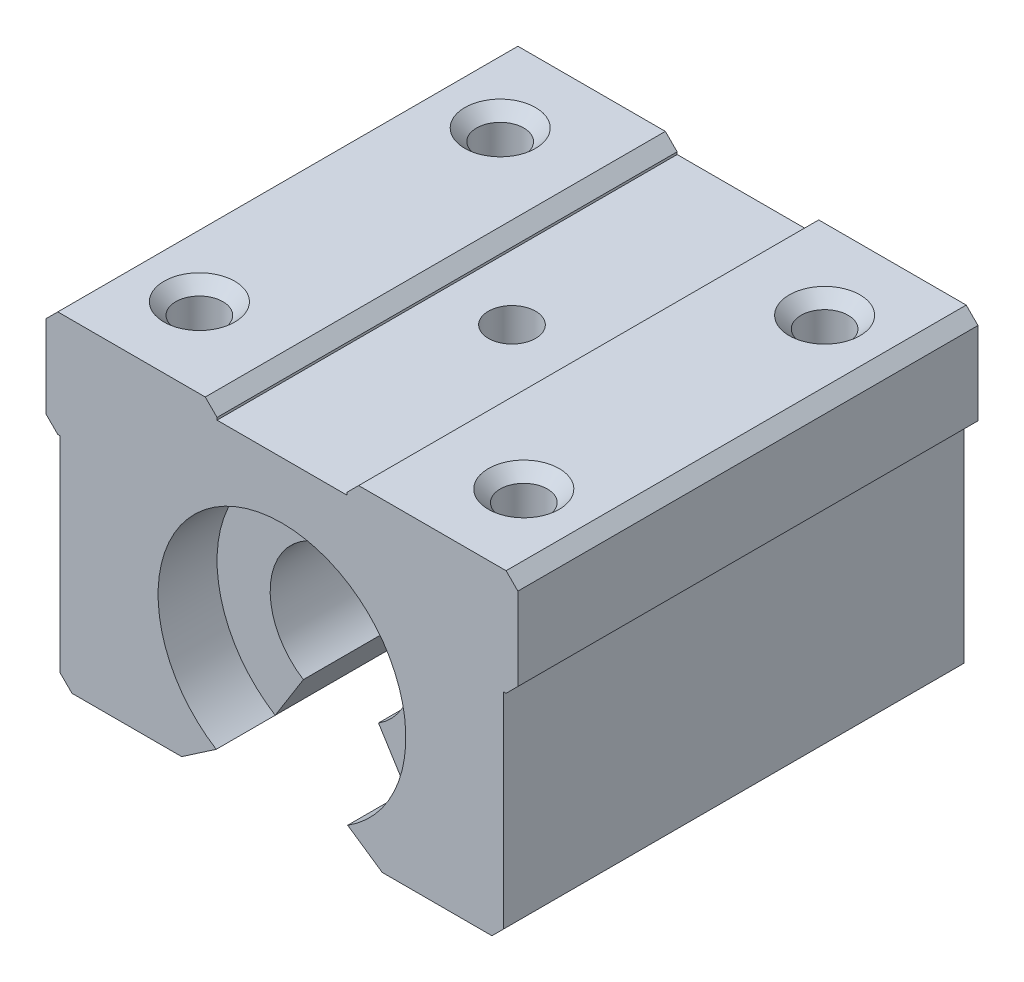
SolidWorks part; units mm, degrees
material "Aleación 1060"
ref_plane "Alzado" through (0, 0, 0) normal (0, 0, 1) x (1, 0, 0)
ref_plane "Planta" through (0, 0, 0) normal (0, 1, 0) x (1, 0, 0)
ref_plane "Vista lateral" through (0, 0, 0) normal (1, 0, 0) x (0, 0, -1)
sketch "Croquis1" plane through (0, 0, 0) normal (0, 0, 1) x (1, 0, 0)
  line L0 (-18.8, -12.5) -> (-18.8, 12.5) construction
  line L1 (-20, -13.7) -> (20, -13.7) construction
  line L2 (-20, -13.7) -> (-20, 13.7) construction
  line L3 (-20, 13.7) -> (20, 13.7) construction
  line L4 (20, -13.7) -> (20, 13.7) construction
  line L5 (-20, -13.7) -> (20, 13.7) construction
  line L6 (-20, 13.7) -> (20, -13.7) construction
  line L7 (-18.8, 12.5) -> (18.8, 12.5) construction
  line L8 (18.8, -12.5) -> (18.8, 12.5) construction
  line L9 (-18.8, -12.5) -> (18.8, -12.5) construction
  line L10 (-5.5, 13.7) -> (-5.5, -13.7) construction
  line L11 (5.5, 13.7) -> (5.5, -13.7) construction
  line L12 (-20, 4.7) -> (20, 4.7) construction
  line L13 (-5.5, 13.7) -> (-5.5, 12.5)
  line L14 (-5.5, 12.5) -> (5.5, 12.5)
  line L15 (5.5, 12.5) -> (5.5, 13.7)
  line L16 (5.5, 13.7) -> (20, 13.7)
  line L17 (20, 13.7) -> (20, 4.7)
  line L18 (20, 4.7) -> (18.8, 4.7)
  line L19 (18.8, 4.7) -> (18.8, -13.7)
  line L20 (18.8, -13.7) -> (-18.8, -13.7)
  line L21 (-18.8, -13.7) -> (-18.8, 4.7)
  line L22 (-18.8, 4.7) -> (-20, 4.7)
  line L23 (-20, 4.7) -> (-20, 13.7)
  line L24 (-20, 13.7) -> (-5.5, 13.7)
  point P0 (0, 0)
  dimension "D1" = 40
  dimension "D2" = 27.4
  dimension "D4" = 5.5
  dimension "D5" = 5.5
  dimension "D6" = 9
  dimension "D3" = 1.2
extrude "Saliente-Extruir1" add sketch "Croquis1" along normal blind 39
sketch "Croquis2" plane through (0, 0, 39) normal (0, 0, 1) x (1, 0, 0)
  line L0 (-18.8, -2.8) -> (18.8, -2.8) construction
  line L1 (-18.8, 4.7) -> (-18.8, -13.7) construction
  line L2 (18.8, -13.7) -> (18.8, 4.7) construction
  line L3 (-5.5, 13.7) -> (-20, 13.7) construction
  line L4 (0, -13.7) -> (0, -2.8) construction
  line L5 (-18.8, -13.7) -> (18.8, -13.7) construction
  line L6 (-18.8, -11.7) -> (18.8, -11.7) construction
  line L7 (-8.5, -13.7) -> (-5.5714, -11.7)
  line L8 (8.5, -13.7) -> (5.5714, -11.7)
  line L9 (-8.5, -13.7) -> (8.5, -13.7)
  circle A0 centre (0, -2.8) radius 10.5 construction
  arc A1 (-5.5714, -11.7) -> (5.5714, -11.7) centre (0, -2.8) cw
  point P13 (-8.5, -13.7)
  line M15 (-18.8, -13.7) -> (18.8, -13.7)
  dimension "D2" = 21
  dimension "D1" = 16.5
  dimension "D3" = 8.5
  dimension "D4" = 2
extrude "Cortar-Extruir1" cut sketch "Croquis2" against normal up to surface (39 mm away) contours A1 L7 L8 M15 region at (0, -3.256, 39) up to face at (0, 5.9333, 0)
ref_plane "Plano1" through (0, 0, 5) normal (0, 0, -1) x (-1, 0, 0)
sketch "Croquis3" plane through (0, 0, 5) normal (0, 0, -1) x (-1, 0, 0)
  line L0 (8.5, -13.7) -> (5.5714, -11.7) construction
  line L1 (-8.5, -13.7) -> (-5.5714, -11.7) construction
  line L2 (8.5, -13.7) -> (5.5714, -11.7)
  line L3 (-8.5, -13.7) -> (-5.5714, -11.7)
  line L4 (0, -2.8) -> (-5.5714, -11.7) construction
  line L5 (0, -2.8) -> (5.5714, -11.7) construction
  line L6 (-3.1836, -7.8857) -> (-5.5714, -11.7)
  line L7 (3.1836, -7.8857) -> (5.5714, -11.7)
  arc A0 (5.5714, -11.7) -> (-5.5714, -11.7) centre (0, -2.8) ccw construction
  arc A1 (5.5714, -11.7) -> (-5.5714, -11.7) centre (0, -2.8) ccw
  circle A2 centre (0, -2.8) radius 6 construction
  arc A3 (-3.1836, -7.8857) -> (3.1836, -7.8857) centre (0, -2.8) cw
  dimension "D1" = 12
extrude "Saliente-Extruir2" add sketch "Croquis3" against normal blind 29 contours L6 A3 L7 A1 region at (4.6198, -9.6412, 5)
sketch "Croquis5" plane through (0, 13.7, 0) normal (0, 1, 0) x (1, 0, 0)
  line L0 (20, 0) -> (-20, -39) construction
  line L2 (13.75, -32.25) -> (-13.75, -32.25) construction
  line L3 (13.75, -32.25) -> (13.75, -6.75) construction
  line L4 (13.75, -6.75) -> (-13.75, -6.75) construction
  line L5 (-13.75, -32.25) -> (-13.75, -6.75) construction
  line L6 (13.75, -32.25) -> (-13.75, -6.75) construction
  line L7 (13.75, -6.75) -> (-13.75, -32.25) construction
  circle A0 centre (13.75, -32.25) radius 2
  circle A1 centre (-13.75, -32.25) radius 2
  circle A2 centre (13.75, -6.75) radius 2
  circle A3 centre (-13.75, -6.75) radius 2
  point P4 (0, -19.5)
  dimension "D3" = 4
  dimension "D1" = 27.5
  dimension "D2" = 25.5
extrude "Cortar-Extruir2" cut sketch "Croquis5" against normal blind 17
sketch "Croquis6" plane through (0, 12.5, 0) normal (0, 1, 0) x (1, 0, 0)
  line L0 (5.5, -19.5) -> (-5.5, -19.5) construction
  line L1 (5.5, -39) -> (5.5, 0) construction
  line L2 (-5.5, -39) -> (-5.5, 0) construction
  circle A0 centre (0, -19.5) radius 2
  dimension "D1" = 4
extrude "Cortar-Extruir3" cut sketch "Croquis6" against normal blind 4
chamfer "Chaflán1" distance 1 angle 45 12 edges at (-18.8, -13.7, 19.5) (18.8, -13.7, 19.5) (20, 4.7, 19.5) (-20, 4.7, 19.5) (-20, 13.7, 19.5) (20, 13.7, 19.5) (-5.5, 13.7, 19.5) (5.5, 13.7, 19.5) (-13.75, 13.7, 8.75) (-13.75, 13.7, 34.25) (13.75, 13.7, 34.25) (13.75, 13.7, 8.75)
ref_axis "Eje1" through (0, -2.8, 34) along (0, 0, -1)
ref_plane "Plano2" through (0, -2.8, 0) normal (0, 1, 0) x (1, 0, 0)
equation "\"D3@Croquis2\"=17/2"
